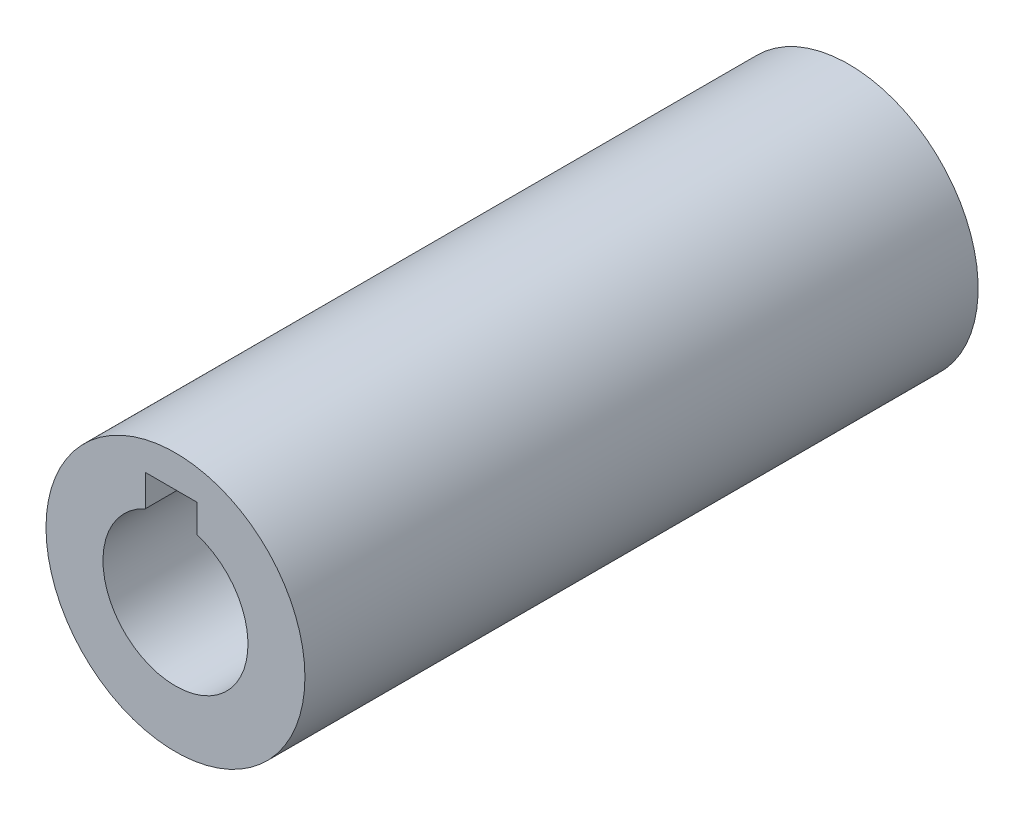
SolidWorks part; units mm, degrees
ref_plane "Front Plane" through (0, 0, 0) normal (0, 0, 1) x (1, 0, 0)
ref_plane "Top Plane" through (0, 0, 0) normal (0, 1, 0) x (1, 0, 0)
ref_plane "Right Plane" through (0, 0, 0) normal (1, 0, 0) x (0, 0, -1)
sketch "Sketch1" plane through (0, 0, 0) normal (0, 0, 1) x (1, 0, 0)
  line L2 (-2.9167, 6.3634) -> (-2.9167, 9.4091)
  line L3 (-2.9167, 9.4091) -> (2.0833, 9.4091)
  line L4 (2.0833, 6.6828) -> (2.0833, 9.4091)
  arc A0 (-2.9167, 6.3634) -> (2.0833, 6.6828) centre (0, 0) ccw
  circle A1 centre (0, 0) radius 12.5
  point P3 (0, 7)
  dimension "D1" = 14
  dimension "D3" = 25
  dimension "D2" = 5
extrude "Boss-Extrude1" add sketch "Sketch1" along normal blind 30
sketch "Sketch3" plane through (0, 0, 0) normal (0, 0, -1) x (-1, 0, 0)
  line L2 (-1.25, 5.8683) -> (-1.25, 7.8557)
  line L3 (-1.25, 7.8557) -> (1.25, 7.8557)
  line L4 (1.25, 5.8683) -> (1.25, 7.8557)
  arc A0 (-1.25, 5.8683) -> (1.25, 5.8683) centre (0, 0) ccw
  circle A1 centre (0, 0) radius 12.5
  point P1 (0, 7.8557)
  point P3 (0, 6)
  dimension "D1" = 6
  dimension "D3" = 25
  dimension "D2" = 2.5
sketch "Sketch4" plane through (0, 0, 0) normal (0, 0, -1) x (-1, 0, 0)
  circle A0 centre (0, 0) radius 12.5 construction
  circle A1 centre (0, 0) radius 12.5
extrude "Boss-Extrude2" add sketch "Sketch4" along normal blind 5
sketch "Sketch5" plane through (0, 0, -5) normal (0, 0, -1) x (-1, 0, 0)
  line L0 (1.25, 5.8683) -> (1.25, 7.8557) construction
  line L1 (-1.25, 5.8683) -> (-1.25, 7.8557) construction
  line L2 (-1.25, 7.8557) -> (1.25, 7.8557) construction
  line L3 (1.25, 5.8683) -> (1.25, 7.8557)
  line L4 (-1.25, 7.8557) -> (1.25, 7.8557)
  line L5 (-1.25, 5.8683) -> (-1.25, 7.8557)
  arc A0 (-1.25, 5.8683) -> (1.25, 5.8683) centre (0, 0) ccw construction
  circle A1 centre (0, 0) radius 12.5 construction
  circle A2 centre (0, 0) radius 12.5
  circle A3 centre (0, 0) radius 12.5
  circle A4 centre (0, 0) radius 12.5
  arc A5 (-1.25, 5.8683) -> (1.25, 5.8683) centre (0, 0) ccw
  circle A6 centre (0, 0) radius 12.5
  circle M2 centre (0, 0) radius 12.5
  dimension "D2" = 25
  dimension "D1" = 0
extrude "Boss-Extrude3" add sketch "Sketch5" along normal blind 30 contours A5 L5 L4 L3 M2 region at (12.1464, 0, -5)
